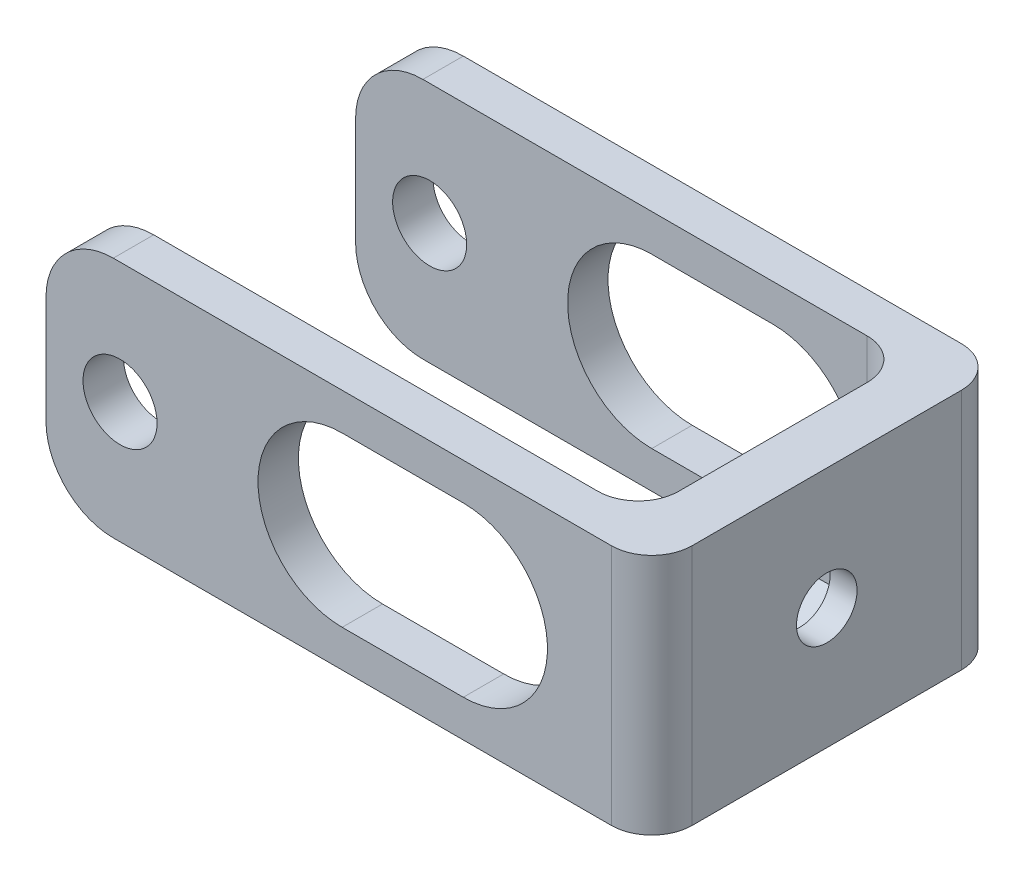
SolidWorks part; units mm, degrees
ref_plane "Front Plane" through (0, 0, 0) normal (0, 0, 1) x (1, 0, 0)
ref_plane "Top Plane" through (0, 0, 0) normal (0, 1, 0) x (1, 0, 0)
ref_plane "Right Plane" through (0, 0, 0) normal (1, 0, 0) x (0, 0, -1)
sketch "Sketch1" plane through (0, 0, 0) normal (1, 0, 0) x (0, 0, -1)
  line L1 (-13, -9) -> (13, -9)
  line L2 (-13, -9) -> (-13, 9)
  line L3 (-13, 9) -> (13, 9)
  line L4 (13, -9) -> (13, 9)
  line L5 (-13, -9) -> (13, 9) construction
  line L6 (-13, 9) -> (13, -9) construction
  point P0 (0, 0)
  dimension "D1" = 18
  dimension "D2" = 26
extrude "Boss-Extrude1" add sketch "Sketch1" along normal blind 4
sketch "Sketch2" plane through (0, 0, 0) normal (-1, 0, 0) x (0, 0, 1)
  line L0 (13, -9) -> (-13, -9) construction
  line L1 (-13, 9) -> (-10, 9)
  line L2 (-13, 9) -> (-13, -9)
  line L3 (-13, -9) -> (-10, -9)
  line L4 (-10, 9) -> (-10, -9)
  line L6 (13, 9) -> (10, 9)
  line L7 (13, 9) -> (13, -9)
  line L8 (13, -9) -> (10, -9)
  line L9 (10, 9) -> (10, -9)
  dimension "D1" = 3
  dimension "D2" = 3
extrude "Boss-Extrude2" add sketch "Sketch2" along normal blind 41
sketch "Sketch3" plane through (0, 0, 13) normal (0, 0, 1) x (1, 0, 0)
  line L1 (-41, -9) -> (-41, 9) construction
  circle A0 centre (-35.5, 0) radius 2.75
  dimension "D1" = 5.5
  dimension "D2" = 5.5
extrude "Cut-Extrude1" cut sketch "Sketch3" against normal through all
fillet "Fillet1" radius 3 4 edges at (0, 0, 10) (4, 0, 13) (4, 0, -13) (0, 0, -10)
fillet "Fillet2" radius 5 4 edges at (-41, 9, -11.5) (-41, -9, -11.5) (-41, -9, 11.5) (-41, 9, 11.5)
sketch "Sketch5" plane through (0, 0, 0) normal (-1, 0, 0) x (0, 0, 1)
  circle A0 centre (0, 0) radius 7
  dimension "D1" = 14
extrude "Boss-Extrude3" add sketch "Sketch5" along normal blind 2
sketch "Sketch7" plane through (4, 0, 0) normal (1, 0, 0) x (0, 0, -1)
  circle A0 centre (0, 0) radius 2.25
  dimension "D1" = 4.5
extrude "Cut-Extrude3" cut sketch "Sketch7" against normal up to next
sketch "Sketch8" plane through (-2, 0, 0) normal (-1, 0, 0) x (0, 0, 1)
  line L1 (0, 4.3301) -> (-3.75, 2.1651)
  line L2 (-3.75, 2.1651) -> (-3.75, -2.1651)
  line L3 (-3.75, -2.1651) -> (0, -4.3301)
  line L4 (0, -4.3301) -> (3.75, -2.1651)
  line L5 (3.75, -2.1651) -> (3.75, 2.1651)
  line L6 (3.75, 2.1651) -> (0, 4.3301)
  circle A0 centre (0, 0) radius 3.75 construction
  dimension "D1" = 7.5
extrude "Cut-Extrude4" cut sketch "Sketch8" against normal blind 4
chamfer "Chamfer1" distance 2 angle 45 2 edges at (0, 7, 0) (0, -7, 0)
sketch "Sketch9" plane through (0, 0, 13) normal (0, 0, 1) x (1, 0, 0)
  line L0 (-41, 0) -> (1, 0) construction
  line L1 (-41, -4) -> (-41, 4) construction
  line L2 (1, -9) -> (1, 9) construction
  line L3 (-19, 0) -> (-10, 0) construction
  line L4 (-19, 6.25) -> (-10, 6.25)
  line L5 (-19, -6.25) -> (-10, -6.25)
  arc A0 (-19, 6.25) -> (-19, -6.25) centre (-19, 0) ccw
  arc A1 (-10, -6.25) -> (-10, 6.25) centre (-10, 0) ccw
  circle A2 centre (-35.5, 0) radius 8.925 construction
  point P8 (-14.5, 0)
  dimension "D2" = 6.25
  dimension "D3" = 17.85
  dimension "D1" = 9
  dimension "D4" = 11
extrude "Cut-Extrude5" cut sketch "Sketch9" against normal through all
